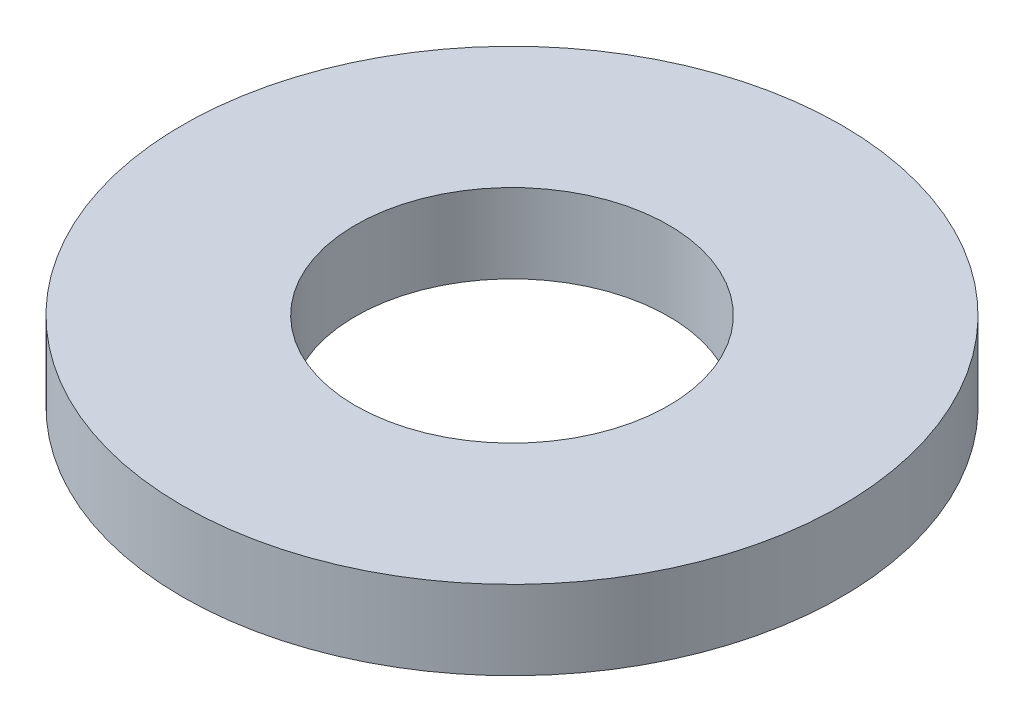
SolidWorks part; units mm, degrees
ref_plane "Front Plane" through (0, 0, 0) normal (0, 0, 1) x (1, 0, 0)
ref_plane "Top Plane" through (0, 0, 0) normal (0, 1, 0) x (1, 0, 0)
ref_plane "Right Plane" through (0, 0, 0) normal (1, 0, 0) x (0, 0, -1)
sketch "Sketch1" plane through (0, 0, 0) normal (0, 1, 0) x (1, 0, 0)
  circle A0 centre (0, 0) radius 100
  dimension "FLANGE_OD" = 200
extrude "Boss-Extrude1" add sketch "Sketch1" along normal blind 24
sketch "Sketch2" plane through (0, 0, 0) normal (0, 1, 0) x (1, 0, 0)
  circle A0 centre (0, 0) radius 47.5
  dimension "BORE_D" = 95
extrude "Cut-Extrude1" cut sketch "Sketch2" along normal through all
sketch "Sketch3" plane through (0, 24, 0) normal (0, 1, 0) x (1, 0, 0)
  circle A0 centre (0, 0) radius 37.0068 construction
  circle A1 centre (-37.0068, 0) radius 6.7826
  dimension "BOLT_D" = 13.5651
  dimension "BOLT_PCD" = 74.0137
extrude "Cut-Extrude2" cut sketch "Sketch3" against normal blind 20.2948 rebuild error yes
pattern_circular "CirPattern1" count 4 over 360 rebuild error yes
